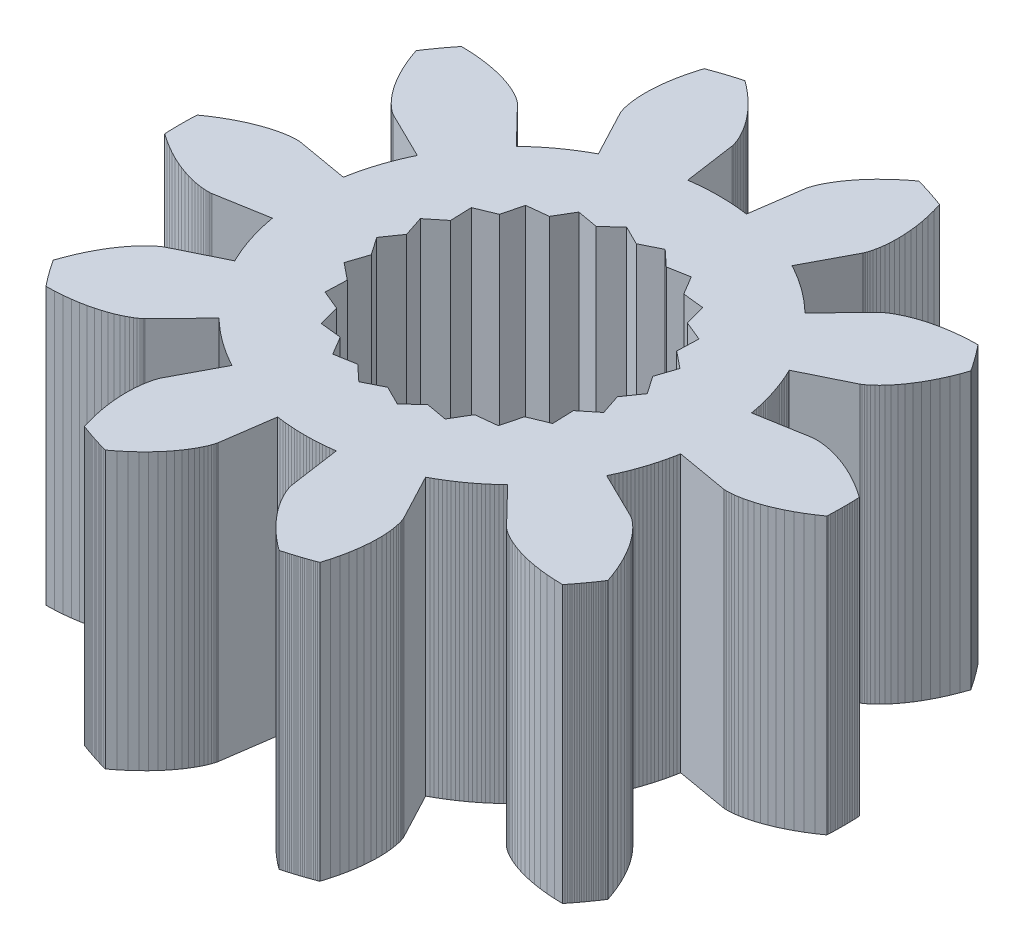
SolidWorks part; units mm, degrees
ref_plane "Front Plane" through (0, 0, 0) normal (0, 0, 1) x (1, 0, 0)
ref_plane "Top Plane" through (0, 0, 0) normal (0, 1, 0) x (1, 0, 0)
ref_plane "Right Plane" through (0, 0, 0) normal (1, 0, 0) x (0, 0, -1)
sketch "Sketch1" plane through (0, 0, 0) normal (0, 1, 0) x (1, 0, 0)
  line L0 (3.6947, -0.6418) -> (4.6291, -0.8041)
  line L1 (4.6291, -0.8041) -> (4.6332, -0.8047)
  line L2 (4.6332, -0.8047) -> (4.6455, -0.806)
  line L3 (4.6455, -0.806) -> (4.6659, -0.8073)
  line L4 (4.6659, -0.8073) -> (4.6947, -0.8081)
  line L5 (4.6947, -0.8081) -> (4.7316, -0.8074)
  line L6 (4.7316, -0.8074) -> (4.7767, -0.8048)
  line L7 (4.7767, -0.8048) -> (4.8297, -0.7994)
  line L8 (4.8297, -0.7994) -> (4.8907, -0.7907)
  line L9 (4.8907, -0.7907) -> (4.9593, -0.778)
  line L10 (4.9593, -0.778) -> (5.0353, -0.7605)
  line L11 (5.0353, -0.7605) -> (5.1184, -0.7378)
  line L12 (5.1184, -0.7378) -> (5.2084, -0.7091)
  line L13 (5.2084, -0.7091) -> (5.3047, -0.6738)
  line L14 (5.3047, -0.6738) -> (5.4071, -0.6314)
  line L15 (5.4071, -0.6314) -> (5.5151, -0.5813)
  line L16 (5.5151, -0.5813) -> (5.6282, -0.523)
  line L17 (5.6282, -0.523) -> (5.7459, -0.456)
  line L18 (5.7459, -0.456) -> (5.8676, -0.3797)
  line L19 (5.8676, -0.3797) -> (5.9928, -0.2937)
  line L20 (5.9928, -0.2937) -> (5.9942, -0.2628)
  line L21 (5.9942, -0.2628) -> (5.9955, -0.2319)
  line L22 (5.9955, -0.2319) -> (5.9966, -0.201)
  line L23 (5.9966, -0.201) -> (5.9976, -0.1701)
  line L24 (5.9976, -0.1701) -> (5.9984, -0.1392)
  line L25 (5.9984, -0.1392) -> (5.999, -0.1083)
  line L26 (5.999, -0.1083) -> (5.9995, -0.0773)
  line L27 (5.9995, -0.0773) -> (5.9998, -0.0464)
  line L28 (5.9998, -0.0464) -> (6, -0.0155)
  line L29 (6, -0.0155) -> (6, 0.0155)
  line L30 (6, 0.0155) -> (5.9998, 0.0464)
  line L31 (5.9998, 0.0464) -> (5.9995, 0.0773)
  line L32 (5.9995, 0.0773) -> (5.999, 0.1083)
  line L33 (5.999, 0.1083) -> (5.9984, 0.1392)
  line L34 (5.9984, 0.1392) -> (5.9976, 0.1701)
  line L35 (5.9976, 0.1701) -> (5.9966, 0.201)
  line L36 (5.9966, 0.201) -> (5.9955, 0.2319)
  line L37 (5.9955, 0.2319) -> (5.9942, 0.2628)
  line L38 (5.9942, 0.2628) -> (5.9928, 0.2937)
  line L39 (5.9928, 0.2937) -> (5.8676, 0.3797)
  line L40 (5.8676, 0.3797) -> (5.7459, 0.456)
  line L41 (5.7459, 0.456) -> (5.6282, 0.523)
  line L42 (5.6282, 0.523) -> (5.5151, 0.5813)
  line L43 (5.5151, 0.5813) -> (5.4071, 0.6314)
  line L44 (5.4071, 0.6314) -> (5.3047, 0.6738)
  line L45 (5.3047, 0.6738) -> (5.2084, 0.7091)
  line L46 (5.2084, 0.7091) -> (5.1184, 0.7378)
  line L47 (5.1184, 0.7378) -> (5.0353, 0.7605)
  line L48 (5.0353, 0.7605) -> (4.9593, 0.778)
  line L49 (4.9593, 0.778) -> (4.8907, 0.7907)
  line L50 (4.8907, 0.7907) -> (4.8297, 0.7994)
  line L51 (4.8297, 0.7994) -> (4.7767, 0.8048)
  line L52 (4.7767, 0.8048) -> (4.7316, 0.8074)
  line L53 (4.7316, 0.8074) -> (4.6947, 0.8081)
  line L54 (4.6947, 0.8081) -> (4.6659, 0.8073)
  line L55 (4.6659, 0.8073) -> (4.6455, 0.806)
  line L56 (4.6455, 0.806) -> (4.6332, 0.8047)
  line L57 (4.6332, 0.8047) -> (4.6291, 0.8041)
  line L58 (4.6291, 0.8041) -> (3.6947, 0.6418)
  line L59 (3.6947, 0.6418) -> (3.6847, 0.697)
  line L60 (3.6847, 0.697) -> (3.6738, 0.752)
  line L61 (3.6738, 0.752) -> (3.6621, 0.8069)
  line L62 (3.6621, 0.8069) -> (3.6497, 0.8617)
  line L63 (3.6497, 0.8617) -> (3.6364, 0.9162)
  line L64 (3.6364, 0.9162) -> (3.6222, 0.9705)
  line L65 (3.6222, 0.9705) -> (3.6073, 1.0246)
  line L66 (3.6073, 1.0246) -> (3.5916, 1.0785)
  line L67 (3.5916, 1.0785) -> (3.575, 1.1321)
  line L68 (3.575, 1.1321) -> (3.5577, 1.1855)
  line L69 (3.5577, 1.1855) -> (3.5396, 1.2386)
  line L70 (3.5396, 1.2386) -> (3.5206, 1.2914)
  line L71 (3.5206, 1.2914) -> (3.5009, 1.344)
  line L72 (3.5009, 1.344) -> (3.4804, 1.3962)
  line L73 (3.4804, 1.3962) -> (3.4591, 1.4481)
  line L74 (3.4591, 1.4481) -> (3.4371, 1.4997)
  line L75 (3.4371, 1.4997) -> (3.4142, 1.551)
  line L76 (3.4142, 1.551) -> (3.3906, 1.6019)
  line L77 (3.3906, 1.6019) -> (3.3663, 1.6525)
  line L78 (3.3663, 1.6525) -> (4.2177, 2.0704)
  line L79 (4.2177, 2.0704) -> (4.2213, 2.0723)
  line L80 (4.2213, 2.0723) -> (4.232, 2.0785)
  line L81 (4.232, 2.0785) -> (4.2494, 2.0894)
  line L82 (4.2494, 2.0894) -> (4.273, 2.1057)
  line L83 (4.273, 2.1057) -> (4.3025, 2.1279)
  line L84 (4.3025, 2.1279) -> (4.3374, 2.1566)
  line L85 (4.3374, 2.1566) -> (4.3773, 2.1921)
  line L86 (4.3773, 2.1921) -> (4.4214, 2.235)
  line L87 (4.4214, 2.235) -> (4.4694, 2.2856)
  line L88 (4.4694, 2.2856) -> (4.5207, 2.3444)
  line L89 (4.5207, 2.3444) -> (4.5746, 2.4117)
  line L90 (4.5746, 2.4117) -> (4.6304, 2.4877)
  line L91 (4.6304, 2.4877) -> (4.6877, 2.5729)
  line L92 (4.6877, 2.5729) -> (4.7456, 2.6674)
  line L93 (4.7456, 2.6674) -> (4.8035, 2.7714)
  line L94 (4.8035, 2.7714) -> (4.8607, 2.885)
  line L95 (4.8607, 2.885) -> (4.9165, 3.0085)
  line L96 (4.9165, 3.0085) -> (4.9702, 3.1417)
  line L97 (4.9702, 3.1417) -> (5.0209, 3.2848)
  line L98 (5.0209, 3.2848) -> (5.0039, 3.3107)
  line L99 (5.0039, 3.3107) -> (4.9868, 3.3364)
  line L100 (4.9868, 3.3364) -> (4.9695, 3.3621)
  line L101 (4.9695, 3.3621) -> (4.9521, 3.3877)
  line L102 (4.9521, 3.3877) -> (4.9346, 3.4132)
  line L103 (4.9346, 3.4132) -> (4.9169, 3.4386)
  line L104 (4.9169, 3.4386) -> (4.8992, 3.4639)
  line L105 (4.8992, 3.4639) -> (4.8812, 3.4891)
  line L106 (4.8812, 3.4891) -> (4.8632, 3.5142)
  line L107 (4.8632, 3.5142) -> (4.845, 3.5392)
  line L108 (4.845, 3.5392) -> (4.8267, 3.5641)
  line L109 (4.8267, 3.5641) -> (4.8082, 3.589)
  line L110 (4.8082, 3.589) -> (4.7897, 3.6137)
  line L111 (4.7897, 3.6137) -> (4.771, 3.6384)
  line L112 (4.771, 3.6384) -> (4.7522, 3.6629)
  line L113 (4.7522, 3.6629) -> (4.7332, 3.6874)
  line L114 (4.7332, 3.6874) -> (4.7141, 3.7117)
  line L115 (4.7141, 3.7117) -> (4.6949, 3.736)
  line L116 (4.6949, 3.736) -> (4.6756, 3.7601)
  line L117 (4.6756, 3.7601) -> (4.5238, 3.7561)
  line L118 (4.5238, 3.7561) -> (4.3805, 3.7462)
  line L119 (4.3805, 3.7462) -> (4.2459, 3.7313)
  line L120 (4.2459, 3.7313) -> (4.1201, 3.712)
  line L121 (4.1201, 3.712) -> (4.0033, 3.6891)
  line L122 (4.0033, 3.6891) -> (3.8956, 3.6632)
  line L123 (3.8956, 3.6632) -> (3.7969, 3.6351)
  line L124 (3.7969, 3.6351) -> (3.7072, 3.6054)
  line L125 (3.7072, 3.6054) -> (3.6266, 3.575)
  line L126 (3.6266, 3.575) -> (3.5549, 3.5444)
  line L127 (3.5549, 3.5444) -> (3.4919, 3.5144)
  line L128 (3.4919, 3.5144) -> (3.4374, 3.4856)
  line L129 (3.4374, 3.4856) -> (3.3914, 3.4587)
  line L130 (3.3914, 3.4587) -> (3.3533, 3.4344)
  line L131 (3.3533, 3.4344) -> (3.3231, 3.4132)
  line L132 (3.3231, 3.4132) -> (3.3003, 3.3957)
  line L133 (3.3003, 3.3957) -> (3.2845, 3.3826)
  line L134 (3.2845, 3.3826) -> (3.2754, 3.3743)
  line L135 (3.2754, 3.3743) -> (3.2724, 3.3715)
  line L136 (3.2724, 3.3715) -> (2.6118, 2.6909)
  line L137 (2.6118, 2.6909) -> (2.5713, 2.7297)
  line L138 (2.5713, 2.7297) -> (2.5301, 2.7678)
  line L139 (2.5301, 2.7678) -> (2.4884, 2.8054)
  line L140 (2.4884, 2.8054) -> (2.4462, 2.8423)
  line L141 (2.4462, 2.8423) -> (2.4034, 2.8786)
  line L142 (2.4034, 2.8786) -> (2.36, 2.9142)
  line L143 (2.36, 2.9142) -> (2.3161, 2.9492)
  line L144 (2.3161, 2.9492) -> (2.2717, 2.9836)
  line L145 (2.2717, 2.9836) -> (2.2268, 3.0172)
  line L146 (2.2268, 3.0172) -> (2.1814, 3.0502)
  line L147 (2.1814, 3.0502) -> (2.1355, 3.0825)
  line L148 (2.1355, 3.0825) -> (2.0892, 3.1141)
  line L149 (2.0892, 3.1141) -> (2.0423, 3.1451)
  line L150 (2.0423, 3.1451) -> (1.995, 3.1753)
  line L151 (1.995, 3.1753) -> (1.9473, 3.2048)
  line L152 (1.9473, 3.2048) -> (1.8991, 3.2336)
  line L153 (1.8991, 3.2336) -> (1.8505, 3.2616)
  line L154 (1.8505, 3.2616) -> (1.8015, 3.2889)
  line L155 (1.8015, 3.2889) -> (1.7521, 3.3155)
  line L156 (1.7521, 3.3155) -> (2.1952, 4.1541)
  line L157 (2.1952, 4.1541) -> (2.197, 4.1578)
  line L158 (2.197, 4.1578) -> (2.2021, 4.169)
  line L159 (2.2021, 4.169) -> (2.2097, 4.1881)
  line L160 (2.2097, 4.1881) -> (2.2192, 4.2152)
  line L161 (2.2192, 4.2152) -> (2.23, 4.2505)
  line L162 (2.23, 4.2505) -> (2.2415, 4.2942)
  line L163 (2.2415, 4.2942) -> (2.2528, 4.3463)
  line L164 (2.2528, 4.3463) -> (2.2633, 4.407)
  line L165 (2.2633, 4.407) -> (2.2724, 4.4762)
  line L166 (2.2724, 4.4762) -> (2.2793, 4.5538)
  line L167 (2.2793, 4.5538) -> (2.2834, 4.6399)
  line L168 (2.2834, 4.6399) -> (2.2838, 4.7343)
  line L169 (2.2838, 4.7343) -> (2.2801, 4.8369)
  line L170 (2.2801, 4.8369) -> (2.2714, 4.9474)
  line L171 (2.2714, 4.9474) -> (2.2571, 5.0655)
  line L172 (2.2571, 5.0655) -> (2.2366, 5.1911)
  line L173 (2.2366, 5.1911) -> (2.2092, 5.3237)
  line L174 (2.2092, 5.3237) -> (2.1743, 5.4631)
  line L175 (2.1743, 5.4631) -> (2.1312, 5.6087)
  line L176 (2.1312, 5.6087) -> (2.1023, 5.6196)
  line L177 (2.1023, 5.6196) -> (2.0733, 5.6304)
  line L178 (2.0733, 5.6304) -> (2.0442, 5.641)
  line L179 (2.0442, 5.641) -> (2.0151, 5.6515)
  line L180 (2.0151, 5.6515) -> (1.986, 5.6618)
  line L181 (1.986, 5.6618) -> (1.9568, 5.672)
  line L182 (1.9568, 5.672) -> (1.9275, 5.682)
  line L183 (1.9275, 5.682) -> (1.8982, 5.6918)
  line L184 (1.8982, 5.6918) -> (1.8688, 5.7015)
  line L185 (1.8688, 5.7015) -> (1.8394, 5.7111)
  line L186 (1.8394, 5.7111) -> (1.8099, 5.7205)
  line L187 (1.8099, 5.7205) -> (1.7804, 5.7298)
  line L188 (1.7804, 5.7298) -> (1.7508, 5.7389)
  line L189 (1.7508, 5.7389) -> (1.7212, 5.7478)
  line L190 (1.7212, 5.7478) -> (1.6916, 5.7566)
  line L191 (1.6916, 5.7566) -> (1.6619, 5.7653)
  line L192 (1.6619, 5.7653) -> (1.6321, 5.7737)
  line L193 (1.6321, 5.7737) -> (1.6023, 5.7821)
  line L194 (1.6023, 5.7821) -> (1.5725, 5.7903)
  line L195 (1.5725, 5.7903) -> (1.4521, 5.6977)
  line L196 (1.4521, 5.6977) -> (1.3419, 5.6055)
  line L197 (1.3419, 5.6055) -> (1.2418, 5.5143)
  line L198 (1.2418, 5.5143) -> (1.1514, 5.4248)
  line L199 (1.1514, 5.4248) -> (1.0704, 5.3376)
  line L200 (1.0704, 5.3376) -> (0.9984, 5.2533)
  line L201 (0.9984, 5.2533) -> (0.9351, 5.1726)
  line L202 (0.9351, 5.1726) -> (0.88, 5.0959)
  line L203 (0.88, 5.0959) -> (0.8327, 5.0239)
  line L204 (0.8327, 5.0239) -> (0.7926, 4.957)
  line L205 (0.7926, 4.957) -> (0.7593, 4.8957)
  line L206 (0.7593, 4.8957) -> (0.7322, 4.8404)
  line L207 (0.7322, 4.8404) -> (0.7107, 4.7916)
  line L208 (0.7107, 4.7916) -> (0.6942, 4.7495)
  line L209 (0.6942, 4.7495) -> (0.6822, 4.7146)
  line L210 (0.6822, 4.7146) -> (0.674, 4.687)
  line L211 (0.674, 4.687) -> (0.669, 4.6672)
  line L212 (0.669, 4.6672) -> (0.6665, 4.6551)
  line L213 (0.6665, 4.6551) -> (0.6658, 4.6511)
  line L214 (0.6658, 4.6511) -> (0.5314, 3.7122)
  line L215 (0.5314, 3.7122) -> (0.4757, 3.7197)
  line L216 (0.4757, 3.7197) -> (0.42, 3.7264)
  line L217 (0.42, 3.7264) -> (0.3642, 3.7323)
  line L218 (0.3642, 3.7323) -> (0.3083, 3.7373)
  line L219 (0.3083, 3.7373) -> (0.2524, 3.7415)
  line L220 (0.2524, 3.7415) -> (0.1963, 3.7449)
  line L221 (0.1963, 3.7449) -> (0.1403, 3.7474)
  line L222 (0.1403, 3.7474) -> (0.0842, 3.7491)
  line L223 (0.0842, 3.7491) -> (0.0281, 3.7499)
  line L224 (0.0281, 3.7499) -> (-0.0281, 3.7499)
  line L225 (-0.0281, 3.7499) -> (-0.0842, 3.7491)
  line L226 (-0.0842, 3.7491) -> (-0.1403, 3.7474)
  line L227 (-0.1403, 3.7474) -> (-0.1963, 3.7449)
  line L228 (-0.1963, 3.7449) -> (-0.2524, 3.7415)
  line L229 (-0.2524, 3.7415) -> (-0.3083, 3.7373)
  line L230 (-0.3083, 3.7373) -> (-0.3642, 3.7323)
  line L231 (-0.3642, 3.7323) -> (-0.42, 3.7264)
  line L232 (-0.42, 3.7264) -> (-0.4757, 3.7197)
  line L233 (-0.4757, 3.7197) -> (-0.5314, 3.7122)
  line L234 (-0.5314, 3.7122) -> (-0.6658, 4.6511)
  line L235 (-0.6658, 4.6511) -> (-0.6665, 4.6551)
  line L236 (-0.6665, 4.6551) -> (-0.669, 4.6672)
  line L237 (-0.669, 4.6672) -> (-0.674, 4.687)
  line L238 (-0.674, 4.687) -> (-0.6822, 4.7146)
  line L239 (-0.6822, 4.7146) -> (-0.6942, 4.7495)
  line L240 (-0.6942, 4.7495) -> (-0.7107, 4.7916)
  line L241 (-0.7107, 4.7916) -> (-0.7322, 4.8404)
  line L242 (-0.7322, 4.8404) -> (-0.7593, 4.8957)
  line L243 (-0.7593, 4.8957) -> (-0.7926, 4.957)
  line L244 (-0.7926, 4.957) -> (-0.8327, 5.0239)
  line L245 (-0.8327, 5.0239) -> (-0.88, 5.0959)
  line L246 (-0.88, 5.0959) -> (-0.9351, 5.1726)
  line L247 (-0.9351, 5.1726) -> (-0.9984, 5.2533)
  line L248 (-0.9984, 5.2533) -> (-1.0704, 5.3376)
  line L249 (-1.0704, 5.3376) -> (-1.1514, 5.4248)
  line L250 (-1.1514, 5.4248) -> (-1.2418, 5.5143)
  line L251 (-1.2418, 5.5143) -> (-1.3419, 5.6055)
  line L252 (-1.3419, 5.6055) -> (-1.4521, 5.6977)
  line L253 (-1.4521, 5.6977) -> (-1.5725, 5.7903)
  line L254 (-1.5725, 5.7903) -> (-1.6023, 5.7821)
  line L255 (-1.6023, 5.7821) -> (-1.6321, 5.7737)
  line L256 (-1.6321, 5.7737) -> (-1.6619, 5.7653)
  line L257 (-1.6619, 5.7653) -> (-1.6916, 5.7566)
  line L258 (-1.6916, 5.7566) -> (-1.7212, 5.7478)
  line L259 (-1.7212, 5.7478) -> (-1.7508, 5.7389)
  line L260 (-1.7508, 5.7389) -> (-1.7804, 5.7298)
  line L261 (-1.7804, 5.7298) -> (-1.8099, 5.7205)
  line L262 (-1.8099, 5.7205) -> (-1.8394, 5.7111)
  line L263 (-1.8394, 5.7111) -> (-1.8688, 5.7015)
  line L264 (-1.8688, 5.7015) -> (-1.8982, 5.6918)
  line L265 (-1.8982, 5.6918) -> (-1.9275, 5.682)
  line L266 (-1.9275, 5.682) -> (-1.9568, 5.672)
  line L267 (-1.9568, 5.672) -> (-1.986, 5.6618)
  line L268 (-1.986, 5.6618) -> (-2.0151, 5.6515)
  line L269 (-2.0151, 5.6515) -> (-2.0442, 5.641)
  line L270 (-2.0442, 5.641) -> (-2.0733, 5.6304)
  line L271 (-2.0733, 5.6304) -> (-2.1023, 5.6196)
  line L272 (-2.1023, 5.6196) -> (-2.1312, 5.6087)
  line L273 (-2.1312, 5.6087) -> (-2.1743, 5.4631)
  line L274 (-2.1743, 5.4631) -> (-2.2092, 5.3237)
  line L275 (-2.2092, 5.3237) -> (-2.2366, 5.1911)
  line L276 (-2.2366, 5.1911) -> (-2.2571, 5.0655)
  line L277 (-2.2571, 5.0655) -> (-2.2714, 4.9474)
  line L278 (-2.2714, 4.9474) -> (-2.2801, 4.8369)
  line L279 (-2.2801, 4.8369) -> (-2.2838, 4.7343)
  line L280 (-2.2838, 4.7343) -> (-2.2834, 4.6399)
  line L281 (-2.2834, 4.6399) -> (-2.2793, 4.5538)
  line L282 (-2.2793, 4.5538) -> (-2.2724, 4.4762)
  line L283 (-2.2724, 4.4762) -> (-2.2633, 4.407)
  line L284 (-2.2633, 4.407) -> (-2.2528, 4.3463)
  line L285 (-2.2528, 4.3463) -> (-2.2415, 4.2942)
  line L286 (-2.2415, 4.2942) -> (-2.23, 4.2505)
  line L287 (-2.23, 4.2505) -> (-2.2192, 4.2152)
  line L288 (-2.2192, 4.2152) -> (-2.2097, 4.1881)
  line L289 (-2.2097, 4.1881) -> (-2.2021, 4.169)
  line L290 (-2.2021, 4.169) -> (-2.197, 4.1578)
  line L291 (-2.197, 4.1578) -> (-2.1952, 4.1541)
  line L292 (-2.1952, 4.1541) -> (-1.7521, 3.3155)
  line L293 (-1.7521, 3.3155) -> (-1.8015, 3.2889)
  line L294 (-1.8015, 3.2889) -> (-1.8505, 3.2616)
  line L295 (-1.8505, 3.2616) -> (-1.8991, 3.2336)
  line L296 (-1.8991, 3.2336) -> (-1.9473, 3.2048)
  line L297 (-1.9473, 3.2048) -> (-1.995, 3.1753)
  line L298 (-1.995, 3.1753) -> (-2.0423, 3.1451)
  line L299 (-2.0423, 3.1451) -> (-2.0892, 3.1141)
  line L300 (-2.0892, 3.1141) -> (-2.1355, 3.0825)
  line L301 (-2.1355, 3.0825) -> (-2.1814, 3.0502)
  line L302 (-2.1814, 3.0502) -> (-2.2268, 3.0172)
  line L303 (-2.2268, 3.0172) -> (-2.2717, 2.9836)
  line L304 (-2.2717, 2.9836) -> (-2.3161, 2.9492)
  line L305 (-2.3161, 2.9492) -> (-2.36, 2.9142)
  line L306 (-2.36, 2.9142) -> (-2.4034, 2.8786)
  line L307 (-2.4034, 2.8786) -> (-2.4462, 2.8423)
  line L308 (-2.4462, 2.8423) -> (-2.4884, 2.8054)
  line L309 (-2.4884, 2.8054) -> (-2.5301, 2.7678)
  line L310 (-2.5301, 2.7678) -> (-2.5713, 2.7297)
  line L311 (-2.5713, 2.7297) -> (-2.6118, 2.6909)
  line L312 (-2.6118, 2.6909) -> (-3.2724, 3.3715)
  line L313 (-3.2724, 3.3715) -> (-3.2754, 3.3743)
  line L314 (-3.2754, 3.3743) -> (-3.2845, 3.3826)
  line L315 (-3.2845, 3.3826) -> (-3.3003, 3.3957)
  line L316 (-3.3003, 3.3957) -> (-3.3231, 3.4132)
  line L317 (-3.3231, 3.4132) -> (-3.3533, 3.4344)
  line L318 (-3.3533, 3.4344) -> (-3.3914, 3.4587)
  line L319 (-3.3914, 3.4587) -> (-3.4374, 3.4856)
  line L320 (-3.4374, 3.4856) -> (-3.4919, 3.5144)
  line L321 (-3.4919, 3.5144) -> (-3.5549, 3.5444)
  line L322 (-3.5549, 3.5444) -> (-3.6266, 3.575)
  line L323 (-3.6266, 3.575) -> (-3.7072, 3.6054)
  line L324 (-3.7072, 3.6054) -> (-3.7969, 3.6351)
  line L325 (-3.7969, 3.6351) -> (-3.8956, 3.6632)
  line L326 (-3.8956, 3.6632) -> (-4.0033, 3.6891)
  line L327 (-4.0033, 3.6891) -> (-4.1201, 3.712)
  line L328 (-4.1201, 3.712) -> (-4.2459, 3.7313)
  line L329 (-4.2459, 3.7313) -> (-4.3805, 3.7462)
  line L330 (-4.3805, 3.7462) -> (-4.5238, 3.7561)
  line L331 (-4.5238, 3.7561) -> (-4.6756, 3.7601)
  line L332 (-4.6756, 3.7601) -> (-4.6949, 3.736)
  line L333 (-4.6949, 3.736) -> (-4.7141, 3.7117)
  line L334 (-4.7141, 3.7117) -> (-4.7332, 3.6874)
  line L335 (-4.7332, 3.6874) -> (-4.7522, 3.6629)
  line L336 (-4.7522, 3.6629) -> (-4.771, 3.6384)
  line L337 (-4.771, 3.6384) -> (-4.7897, 3.6137)
  line L338 (-4.7897, 3.6137) -> (-4.8082, 3.589)
  line L339 (-4.8082, 3.589) -> (-4.8267, 3.5641)
  line L340 (-4.8267, 3.5641) -> (-4.845, 3.5392)
  line L341 (-4.845, 3.5392) -> (-4.8632, 3.5142)
  line L342 (-4.8632, 3.5142) -> (-4.8812, 3.4891)
  line L343 (-4.8812, 3.4891) -> (-4.8992, 3.4639)
  line L344 (-4.8992, 3.4639) -> (-4.9169, 3.4386)
  line L345 (-4.9169, 3.4386) -> (-4.9346, 3.4132)
  line L346 (-4.9346, 3.4132) -> (-4.9521, 3.3877)
  line L347 (-4.9521, 3.3877) -> (-4.9695, 3.3621)
  line L348 (-4.9695, 3.3621) -> (-4.9868, 3.3364)
  line L349 (-4.9868, 3.3364) -> (-5.0039, 3.3107)
  line L350 (-5.0039, 3.3107) -> (-5.0209, 3.2848)
  line L351 (-5.0209, 3.2848) -> (-4.9702, 3.1417)
  line L352 (-4.9702, 3.1417) -> (-4.9165, 3.0085)
  line L353 (-4.9165, 3.0085) -> (-4.8607, 2.885)
  line L354 (-4.8607, 2.885) -> (-4.8035, 2.7714)
  line L355 (-4.8035, 2.7714) -> (-4.7456, 2.6674)
  line L356 (-4.7456, 2.6674) -> (-4.6877, 2.5729)
  line L357 (-4.6877, 2.5729) -> (-4.6304, 2.4877)
  line L358 (-4.6304, 2.4877) -> (-4.5746, 2.4117)
  line L359 (-4.5746, 2.4117) -> (-4.5207, 2.3444)
  line L360 (-4.5207, 2.3444) -> (-4.4694, 2.2856)
  line L361 (-4.4694, 2.2856) -> (-4.4214, 2.235)
  line L362 (-4.4214, 2.235) -> (-4.3773, 2.1921)
  line L363 (-4.3773, 2.1921) -> (-4.3374, 2.1566)
  line L364 (-4.3374, 2.1566) -> (-4.3025, 2.1279)
  line L365 (-4.3025, 2.1279) -> (-4.273, 2.1057)
  line L366 (-4.273, 2.1057) -> (-4.2494, 2.0894)
  line L367 (-4.2494, 2.0894) -> (-4.232, 2.0785)
  line L368 (-4.232, 2.0785) -> (-4.2213, 2.0723)
  line L369 (-4.2213, 2.0723) -> (-4.2177, 2.0704)
  line L370 (-4.2177, 2.0704) -> (-3.3663, 1.6525)
  line L371 (-3.3663, 1.6525) -> (-3.3906, 1.6019)
  line L372 (-3.3906, 1.6019) -> (-3.4142, 1.551)
  line L373 (-3.4142, 1.551) -> (-3.4371, 1.4997)
  line L374 (-3.4371, 1.4997) -> (-3.4591, 1.4481)
  line L375 (-3.4591, 1.4481) -> (-3.4804, 1.3962)
  line L376 (-3.4804, 1.3962) -> (-3.5009, 1.344)
  line L377 (-3.5009, 1.344) -> (-3.5206, 1.2914)
  line L378 (-3.5206, 1.2914) -> (-3.5396, 1.2386)
  line L379 (-3.5396, 1.2386) -> (-3.5577, 1.1855)
  line L380 (-3.5577, 1.1855) -> (-3.575, 1.1321)
  line L381 (-3.575, 1.1321) -> (-3.5916, 1.0785)
  line L382 (-3.5916, 1.0785) -> (-3.6073, 1.0246)
  line L383 (-3.6073, 1.0246) -> (-3.6222, 0.9705)
  line L384 (-3.6222, 0.9705) -> (-3.6364, 0.9162)
  line L385 (-3.6364, 0.9162) -> (-3.6497, 0.8617)
  line L386 (-3.6497, 0.8617) -> (-3.6621, 0.8069)
  line L387 (-3.6621, 0.8069) -> (-3.6738, 0.752)
  line L388 (-3.6738, 0.752) -> (-3.6847, 0.697)
  line L389 (-3.6847, 0.697) -> (-3.6947, 0.6418)
  line L390 (-3.6947, 0.6418) -> (-4.6291, 0.8041)
  line L391 (-4.6291, 0.8041) -> (-4.6332, 0.8047)
  line L392 (-4.6332, 0.8047) -> (-4.6455, 0.806)
  line L393 (-4.6455, 0.806) -> (-4.6659, 0.8073)
  line L394 (-4.6659, 0.8073) -> (-4.6947, 0.8081)
  line L395 (-4.6947, 0.8081) -> (-4.7316, 0.8074)
  line L396 (-4.7316, 0.8074) -> (-4.7767, 0.8048)
  line L397 (-4.7767, 0.8048) -> (-4.8297, 0.7994)
  line L398 (-4.8297, 0.7994) -> (-4.8907, 0.7907)
  line L399 (-4.8907, 0.7907) -> (-4.9593, 0.778)
  line L400 (-4.9593, 0.778) -> (-5.0353, 0.7605)
  line L401 (-5.0353, 0.7605) -> (-5.1184, 0.7378)
  line L402 (-5.1184, 0.7378) -> (-5.2084, 0.7091)
  line L403 (-5.2084, 0.7091) -> (-5.3047, 0.6738)
  line L404 (-5.3047, 0.6738) -> (-5.4071, 0.6314)
  line L405 (-5.4071, 0.6314) -> (-5.5151, 0.5813)
  line L406 (-5.5151, 0.5813) -> (-5.6282, 0.523)
  line L407 (-5.6282, 0.523) -> (-5.7459, 0.456)
  line L408 (-5.7459, 0.456) -> (-5.8676, 0.3797)
  line L409 (-5.8676, 0.3797) -> (-5.9928, 0.2937)
  line L410 (-5.9928, 0.2937) -> (-5.9942, 0.2628)
  line L411 (-5.9942, 0.2628) -> (-5.9955, 0.2319)
  line L412 (-5.9955, 0.2319) -> (-5.9966, 0.201)
  line L413 (-5.9966, 0.201) -> (-5.9976, 0.1701)
  line L414 (-5.9976, 0.1701) -> (-5.9984, 0.1392)
  line L415 (-5.9984, 0.1392) -> (-5.999, 0.1083)
  line L416 (-5.999, 0.1083) -> (-5.9995, 0.0773)
  line L417 (-5.9995, 0.0773) -> (-5.9998, 0.0464)
  line L418 (-5.9998, 0.0464) -> (-6, 0.0155)
  line L419 (-6, 0.0155) -> (-6, -0.0155)
  line L420 (-6, -0.0155) -> (-5.9998, -0.0464)
  line L421 (-5.9998, -0.0464) -> (-5.9995, -0.0773)
  line L422 (-5.9995, -0.0773) -> (-5.999, -0.1083)
  line L423 (-5.999, -0.1083) -> (-5.9984, -0.1392)
  line L424 (-5.9984, -0.1392) -> (-5.9976, -0.1701)
  line L425 (-5.9976, -0.1701) -> (-5.9966, -0.201)
  line L426 (-5.9966, -0.201) -> (-5.9955, -0.2319)
  line L427 (-5.9955, -0.2319) -> (-5.9942, -0.2628)
  line L428 (-5.9942, -0.2628) -> (-5.9928, -0.2937)
  line L429 (-5.9928, -0.2937) -> (-5.8676, -0.3797)
  line L430 (-5.8676, -0.3797) -> (-5.7459, -0.456)
  line L431 (-5.7459, -0.456) -> (-5.6282, -0.523)
  line L432 (-5.6282, -0.523) -> (-5.5151, -0.5813)
  line L433 (-5.5151, -0.5813) -> (-5.4071, -0.6314)
  line L434 (-5.4071, -0.6314) -> (-5.3047, -0.6738)
  line L435 (-5.3047, -0.6738) -> (-5.2084, -0.7091)
  line L436 (-5.2084, -0.7091) -> (-5.1184, -0.7378)
  line L437 (-5.1184, -0.7378) -> (-5.0353, -0.7605)
  line L438 (-5.0353, -0.7605) -> (-4.9593, -0.778)
  line L439 (-4.9593, -0.778) -> (-4.8907, -0.7907)
  line L440 (-4.8907, -0.7907) -> (-4.8297, -0.7994)
  line L441 (-4.8297, -0.7994) -> (-4.7767, -0.8048)
  line L442 (-4.7767, -0.8048) -> (-4.7316, -0.8074)
  line L443 (-4.7316, -0.8074) -> (-4.6947, -0.8081)
  line L444 (-4.6947, -0.8081) -> (-4.6659, -0.8073)
  line L445 (-4.6659, -0.8073) -> (-4.6455, -0.806)
  line L446 (-4.6455, -0.806) -> (-4.6332, -0.8047)
  line L447 (-4.6332, -0.8047) -> (-4.6291, -0.8041)
  line L448 (-4.6291, -0.8041) -> (-3.6947, -0.6418)
  line L449 (-3.6947, -0.6418) -> (-3.6847, -0.697)
  line L450 (-3.6847, -0.697) -> (-3.6738, -0.752)
  line L451 (-3.6738, -0.752) -> (-3.6621, -0.8069)
  line L452 (-3.6621, -0.8069) -> (-3.6497, -0.8617)
  line L453 (-3.6497, -0.8617) -> (-3.6364, -0.9162)
  line L454 (-3.6364, -0.9162) -> (-3.6222, -0.9705)
  line L455 (-3.6222, -0.9705) -> (-3.6073, -1.0246)
  line L456 (-3.6073, -1.0246) -> (-3.5916, -1.0785)
  line L457 (-3.5916, -1.0785) -> (-3.575, -1.1321)
  line L458 (-3.575, -1.1321) -> (-3.5577, -1.1855)
  line L459 (-3.5577, -1.1855) -> (-3.5396, -1.2386)
  line L460 (-3.5396, -1.2386) -> (-3.5206, -1.2914)
  line L461 (-3.5206, -1.2914) -> (-3.5009, -1.344)
  line L462 (-3.5009, -1.344) -> (-3.4804, -1.3962)
  line L463 (-3.4804, -1.3962) -> (-3.4591, -1.4481)
  line L464 (-3.4591, -1.4481) -> (-3.4371, -1.4997)
  line L465 (-3.4371, -1.4997) -> (-3.4142, -1.551)
  line L466 (-3.4142, -1.551) -> (-3.3906, -1.6019)
  line L467 (-3.3906, -1.6019) -> (-3.3663, -1.6525)
  line L468 (-3.3663, -1.6525) -> (-4.2177, -2.0704)
  line L469 (-4.2177, -2.0704) -> (-4.2213, -2.0723)
  line L470 (-4.2213, -2.0723) -> (-4.232, -2.0785)
  line L471 (-4.232, -2.0785) -> (-4.2494, -2.0894)
  line L472 (-4.2494, -2.0894) -> (-4.273, -2.1057)
  line L473 (-4.273, -2.1057) -> (-4.3025, -2.1279)
  line L474 (-4.3025, -2.1279) -> (-4.3374, -2.1566)
  line L475 (-4.3374, -2.1566) -> (-4.3773, -2.1921)
  line L476 (-4.3773, -2.1921) -> (-4.4214, -2.235)
  line L477 (-4.4214, -2.235) -> (-4.4694, -2.2856)
  line L478 (-4.4694, -2.2856) -> (-4.5207, -2.3444)
  line L479 (-4.5207, -2.3444) -> (-4.5746, -2.4117)
  line L480 (-4.5746, -2.4117) -> (-4.6304, -2.4877)
  line L481 (-4.6304, -2.4877) -> (-4.6877, -2.5729)
  line L482 (-4.6877, -2.5729) -> (-4.7456, -2.6674)
  line L483 (-4.7456, -2.6674) -> (-4.8035, -2.7714)
  line L484 (-4.8035, -2.7714) -> (-4.8607, -2.885)
  line L485 (-4.8607, -2.885) -> (-4.9165, -3.0085)
  line L486 (-4.9165, -3.0085) -> (-4.9702, -3.1417)
  line L487 (-4.9702, -3.1417) -> (-5.0209, -3.2848)
  line L488 (-5.0209, -3.2848) -> (-5.0039, -3.3107)
  line L489 (-5.0039, -3.3107) -> (-4.9868, -3.3364)
  line L490 (-4.9868, -3.3364) -> (-4.9695, -3.3621)
  line L491 (-4.9695, -3.3621) -> (-4.9521, -3.3877)
  line L492 (-4.9521, -3.3877) -> (-4.9346, -3.4132)
  line L493 (-4.9346, -3.4132) -> (-4.9169, -3.4386)
  line L494 (-4.9169, -3.4386) -> (-4.8992, -3.4639)
  line L495 (-4.8992, -3.4639) -> (-4.8812, -3.4891)
  line L496 (-4.8812, -3.4891) -> (-4.8632, -3.5142)
  line L497 (-4.8632, -3.5142) -> (-4.845, -3.5392)
  line L498 (-4.845, -3.5392) -> (-4.8267, -3.5641)
  line L499 (-4.8267, -3.5641) -> (-4.8082, -3.589)
  line L500 (-4.8082, -3.589) -> (-4.7897, -3.6137)
  line L501 (-4.7897, -3.6137) -> (-4.771, -3.6384)
  line L502 (-4.771, -3.6384) -> (-4.7522, -3.6629)
  line L503 (-4.7522, -3.6629) -> (-4.7332, -3.6874)
  line L504 (-4.7332, -3.6874) -> (-4.7141, -3.7117)
  line L505 (-4.7141, -3.7117) -> (-4.6949, -3.736)
  line L506 (-4.6949, -3.736) -> (-4.6756, -3.7601)
  line L507 (-4.6756, -3.7601) -> (-4.5238, -3.7561)
  line L508 (-4.5238, -3.7561) -> (-4.3805, -3.7462)
  line L509 (-4.3805, -3.7462) -> (-4.2459, -3.7313)
  line L510 (-4.2459, -3.7313) -> (-4.1201, -3.712)
  line L511 (-4.1201, -3.712) -> (-4.0033, -3.6891)
  line L512 (-4.0033, -3.6891) -> (-3.8956, -3.6632)
  line L513 (-3.8956, -3.6632) -> (-3.7969, -3.6351)
  line L514 (-3.7969, -3.6351) -> (-3.7072, -3.6054)
  line L515 (-3.7072, -3.6054) -> (-3.6266, -3.575)
  line L516 (-3.6266, -3.575) -> (-3.5549, -3.5444)
  line L517 (-3.5549, -3.5444) -> (-3.4919, -3.5144)
  line L518 (-3.4919, -3.5144) -> (-3.4374, -3.4856)
  line L519 (-3.4374, -3.4856) -> (-3.3914, -3.4587)
  line L520 (-3.3914, -3.4587) -> (-3.3533, -3.4344)
  line L521 (-3.3533, -3.4344) -> (-3.3231, -3.4132)
  line L522 (-3.3231, -3.4132) -> (-3.3003, -3.3957)
  line L523 (-3.3003, -3.3957) -> (-3.2845, -3.3826)
  line L524 (-3.2845, -3.3826) -> (-3.2754, -3.3743)
  line L525 (-3.2754, -3.3743) -> (-3.2724, -3.3715)
  line L526 (-3.2724, -3.3715) -> (-2.6118, -2.6909)
  line L527 (-2.6118, -2.6909) -> (-2.5713, -2.7297)
  line L528 (-2.5713, -2.7297) -> (-2.5301, -2.7678)
  line L529 (-2.5301, -2.7678) -> (-2.4884, -2.8054)
  line L530 (-2.4884, -2.8054) -> (-2.4462, -2.8423)
  line L531 (-2.4462, -2.8423) -> (-2.4034, -2.8786)
  line L532 (-2.4034, -2.8786) -> (-2.36, -2.9142)
  line L533 (-2.36, -2.9142) -> (-2.3161, -2.9492)
  line L534 (-2.3161, -2.9492) -> (-2.2717, -2.9836)
  line L535 (-2.2717, -2.9836) -> (-2.2268, -3.0172)
  line L536 (-2.2268, -3.0172) -> (-2.1814, -3.0502)
  line L537 (-2.1814, -3.0502) -> (-2.1355, -3.0825)
  line L538 (-2.1355, -3.0825) -> (-2.0892, -3.1141)
  line L539 (-2.0892, -3.1141) -> (-2.0423, -3.1451)
  line L540 (-2.0423, -3.1451) -> (-1.995, -3.1753)
  line L541 (-1.995, -3.1753) -> (-1.9473, -3.2048)
  line L542 (-1.9473, -3.2048) -> (-1.8991, -3.2336)
  line L543 (-1.8991, -3.2336) -> (-1.8505, -3.2616)
  line L544 (-1.8505, -3.2616) -> (-1.8015, -3.2889)
  line L545 (-1.8015, -3.2889) -> (-1.7521, -3.3155)
  line L546 (-1.7521, -3.3155) -> (-2.1952, -4.1541)
  line L547 (-2.1952, -4.1541) -> (-2.197, -4.1578)
  line L548 (-2.197, -4.1578) -> (-2.2021, -4.169)
  line L549 (-2.2021, -4.169) -> (-2.2097, -4.1881)
  line L550 (-2.2097, -4.1881) -> (-2.2192, -4.2152)
  line L551 (-2.2192, -4.2152) -> (-2.23, -4.2505)
  line L552 (-2.23, -4.2505) -> (-2.2415, -4.2942)
  line L553 (-2.2415, -4.2942) -> (-2.2528, -4.3463)
  line L554 (-2.2528, -4.3463) -> (-2.2633, -4.407)
  line L555 (-2.2633, -4.407) -> (-2.2724, -4.4762)
  line L556 (-2.2724, -4.4762) -> (-2.2793, -4.5538)
  line L557 (-2.2793, -4.5538) -> (-2.2834, -4.6399)
  line L558 (-2.2834, -4.6399) -> (-2.2838, -4.7343)
  line L559 (-2.2838, -4.7343) -> (-2.2801, -4.8369)
  line L560 (-2.2801, -4.8369) -> (-2.2714, -4.9474)
  line L561 (-2.2714, -4.9474) -> (-2.2571, -5.0655)
  line L562 (-2.2571, -5.0655) -> (-2.2366, -5.1911)
  line L563 (-2.2366, -5.1911) -> (-2.2092, -5.3237)
  line L564 (-2.2092, -5.3237) -> (-2.1743, -5.4631)
  line L565 (-2.1743, -5.4631) -> (-2.1312, -5.6087)
  line L566 (-2.1312, -5.6087) -> (-2.1023, -5.6196)
  line L567 (-2.1023, -5.6196) -> (-2.0733, -5.6304)
  line L568 (-2.0733, -5.6304) -> (-2.0442, -5.641)
  line L569 (-2.0442, -5.641) -> (-2.0151, -5.6515)
  line L570 (-2.0151, -5.6515) -> (-1.986, -5.6618)
  line L571 (-1.986, -5.6618) -> (-1.9568, -5.672)
  line L572 (-1.9568, -5.672) -> (-1.9275, -5.682)
  line L573 (-1.9275, -5.682) -> (-1.8982, -5.6918)
  line L574 (-1.8982, -5.6918) -> (-1.8688, -5.7015)
  line L575 (-1.8688, -5.7015) -> (-1.8394, -5.7111)
  line L576 (-1.8394, -5.7111) -> (-1.8099, -5.7205)
  line L577 (-1.8099, -5.7205) -> (-1.7804, -5.7298)
  line L578 (-1.7804, -5.7298) -> (-1.7508, -5.7389)
  line L579 (-1.7508, -5.7389) -> (-1.7212, -5.7478)
  line L580 (-1.7212, -5.7478) -> (-1.6916, -5.7566)
  line L581 (-1.6916, -5.7566) -> (-1.6619, -5.7653)
  line L582 (-1.6619, -5.7653) -> (-1.6321, -5.7737)
  line L583 (-1.6321, -5.7737) -> (-1.6023, -5.7821)
  line L584 (-1.6023, -5.7821) -> (-1.5725, -5.7903)
  line L585 (-1.5725, -5.7903) -> (-1.4521, -5.6977)
  line L586 (-1.4521, -5.6977) -> (-1.3419, -5.6055)
  line L587 (-1.3419, -5.6055) -> (-1.2418, -5.5143)
  line L588 (-1.2418, -5.5143) -> (-1.1514, -5.4248)
  line L589 (-1.1514, -5.4248) -> (-1.0704, -5.3376)
  line L590 (-1.0704, -5.3376) -> (-0.9984, -5.2533)
  line L591 (-0.9984, -5.2533) -> (-0.9351, -5.1726)
  line L592 (-0.9351, -5.1726) -> (-0.88, -5.0959)
  line L593 (-0.88, -5.0959) -> (-0.8327, -5.0239)
  line L594 (-0.8327, -5.0239) -> (-0.7926, -4.957)
  line L595 (-0.7926, -4.957) -> (-0.7593, -4.8957)
  line L596 (-0.7593, -4.8957) -> (-0.7322, -4.8404)
  line L597 (-0.7322, -4.8404) -> (-0.7107, -4.7916)
  line L598 (-0.7107, -4.7916) -> (-0.6942, -4.7495)
  line L599 (-0.6942, -4.7495) -> (-0.6822, -4.7146)
  line L600 (-0.6822, -4.7146) -> (-0.674, -4.687)
  line L601 (-0.674, -4.687) -> (-0.669, -4.6672)
  line L602 (-0.669, -4.6672) -> (-0.6665, -4.6551)
  line L603 (-0.6665, -4.6551) -> (-0.6658, -4.6511)
  line L604 (-0.6658, -4.6511) -> (-0.5314, -3.7122)
  line L605 (-0.5314, -3.7122) -> (-0.4757, -3.7197)
  line L606 (-0.4757, -3.7197) -> (-0.42, -3.7264)
  line L607 (-0.42, -3.7264) -> (-0.3642, -3.7323)
  line L608 (-0.3642, -3.7323) -> (-0.3083, -3.7373)
  line L609 (-0.3083, -3.7373) -> (-0.2524, -3.7415)
  line L610 (-0.2524, -3.7415) -> (-0.1963, -3.7449)
  line L611 (-0.1963, -3.7449) -> (-0.1403, -3.7474)
  line L612 (-0.1403, -3.7474) -> (-0.0842, -3.7491)
  line L613 (-0.0842, -3.7491) -> (-0.0281, -3.7499)
  line L614 (-0.0281, -3.7499) -> (0.0281, -3.7499)
  line L615 (0.0281, -3.7499) -> (0.0842, -3.7491)
  line L616 (0.0842, -3.7491) -> (0.1403, -3.7474)
  line L617 (0.1403, -3.7474) -> (0.1963, -3.7449)
  line L618 (0.1963, -3.7449) -> (0.2524, -3.7415)
  line L619 (0.2524, -3.7415) -> (0.3083, -3.7373)
  line L620 (0.3083, -3.7373) -> (0.3642, -3.7323)
  line L621 (0.3642, -3.7323) -> (0.42, -3.7264)
  line L622 (0.42, -3.7264) -> (0.4757, -3.7197)
  line L623 (0.4757, -3.7197) -> (0.5314, -3.7122)
  line L624 (0.5314, -3.7122) -> (0.6658, -4.6511)
  line L625 (0.6658, -4.6511) -> (0.6665, -4.6551)
  line L626 (0.6665, -4.6551) -> (0.669, -4.6672)
  line L627 (0.669, -4.6672) -> (0.674, -4.687)
  line L628 (0.674, -4.687) -> (0.6822, -4.7146)
  line L629 (0.6822, -4.7146) -> (0.6942, -4.7495)
  line L630 (0.6942, -4.7495) -> (0.7107, -4.7916)
  line L631 (0.7107, -4.7916) -> (0.7322, -4.8404)
  line L632 (0.7322, -4.8404) -> (0.7593, -4.8957)
  line L633 (0.7593, -4.8957) -> (0.7926, -4.957)
  line L634 (0.7926, -4.957) -> (0.8327, -5.0239)
  line L635 (0.8327, -5.0239) -> (0.88, -5.0959)
  line L636 (0.88, -5.0959) -> (0.9351, -5.1726)
  line L637 (0.9351, -5.1726) -> (0.9984, -5.2533)
  line L638 (0.9984, -5.2533) -> (1.0704, -5.3376)
  line L639 (1.0704, -5.3376) -> (1.1514, -5.4248)
  line L640 (1.1514, -5.4248) -> (1.2418, -5.5143)
  line L641 (1.2418, -5.5143) -> (1.3419, -5.6055)
  line L642 (1.3419, -5.6055) -> (1.4521, -5.6977)
  line L643 (1.4521, -5.6977) -> (1.5725, -5.7903)
  line L644 (1.5725, -5.7903) -> (1.6023, -5.7821)
  line L645 (1.6023, -5.7821) -> (1.6321, -5.7737)
  line L646 (1.6321, -5.7737) -> (1.6619, -5.7653)
  line L647 (1.6619, -5.7653) -> (1.6916, -5.7566)
  line L648 (1.6916, -5.7566) -> (1.7212, -5.7478)
  line L649 (1.7212, -5.7478) -> (1.7508, -5.7389)
  line L650 (1.7508, -5.7389) -> (1.7804, -5.7298)
  line L651 (1.7804, -5.7298) -> (1.8099, -5.7205)
  line L652 (1.8099, -5.7205) -> (1.8394, -5.7111)
  line L653 (1.8394, -5.7111) -> (1.8688, -5.7015)
  line L654 (1.8688, -5.7015) -> (1.8982, -5.6918)
  line L655 (1.8982, -5.6918) -> (1.9275, -5.682)
  line L656 (1.9275, -5.682) -> (1.9568, -5.672)
  line L657 (1.9568, -5.672) -> (1.986, -5.6618)
  line L658 (1.986, -5.6618) -> (2.0151, -5.6515)
  line L659 (2.0151, -5.6515) -> (2.0442, -5.641)
  line L660 (2.0442, -5.641) -> (2.0733, -5.6304)
  line L661 (2.0733, -5.6304) -> (2.1023, -5.6196)
  line L662 (2.1023, -5.6196) -> (2.1312, -5.6087)
  line L663 (2.1312, -5.6087) -> (2.1743, -5.4631)
  line L664 (2.1743, -5.4631) -> (2.2092, -5.3237)
  line L665 (2.2092, -5.3237) -> (2.2366, -5.1911)
  line L666 (2.2366, -5.1911) -> (2.2571, -5.0655)
  line L667 (2.2571, -5.0655) -> (2.2714, -4.9474)
  line L668 (2.2714, -4.9474) -> (2.2801, -4.8369)
  line L669 (2.2801, -4.8369) -> (2.2838, -4.7343)
  line L670 (2.2838, -4.7343) -> (2.2834, -4.6399)
  line L671 (2.2834, -4.6399) -> (2.2793, -4.5538)
  line L672 (2.2793, -4.5538) -> (2.2724, -4.4762)
  line L673 (2.2724, -4.4762) -> (2.2633, -4.407)
  line L674 (2.2633, -4.407) -> (2.2528, -4.3463)
  line L675 (2.2528, -4.3463) -> (2.2415, -4.2942)
  line L676 (2.2415, -4.2942) -> (2.23, -4.2505)
  line L677 (2.23, -4.2505) -> (2.2192, -4.2152)
  line L678 (2.2192, -4.2152) -> (2.2097, -4.1881)
  line L679 (2.2097, -4.1881) -> (2.2021, -4.169)
  line L680 (2.2021, -4.169) -> (2.197, -4.1578)
  line L681 (2.197, -4.1578) -> (2.1952, -4.1541)
  line L682 (2.1952, -4.1541) -> (1.7521, -3.3155)
  line L683 (1.7521, -3.3155) -> (1.8015, -3.2889)
  line L684 (1.8015, -3.2889) -> (1.8505, -3.2616)
  line L685 (1.8505, -3.2616) -> (1.8991, -3.2336)
  line L686 (1.8991, -3.2336) -> (1.9473, -3.2048)
  line L687 (1.9473, -3.2048) -> (1.995, -3.1753)
  line L688 (1.995, -3.1753) -> (2.0423, -3.1451)
  line L689 (2.0423, -3.1451) -> (2.0892, -3.1141)
  line L690 (2.0892, -3.1141) -> (2.1355, -3.0825)
  line L691 (2.1355, -3.0825) -> (2.1814, -3.0502)
  line L692 (2.1814, -3.0502) -> (2.2268, -3.0172)
  line L693 (2.2268, -3.0172) -> (2.2717, -2.9836)
  line L694 (2.2717, -2.9836) -> (2.3161, -2.9492)
  line L695 (2.3161, -2.9492) -> (2.36, -2.9142)
  line L696 (2.36, -2.9142) -> (2.4034, -2.8786)
  line L697 (2.4034, -2.8786) -> (2.4462, -2.8423)
  line L698 (2.4462, -2.8423) -> (2.4884, -2.8054)
  line L699 (2.4884, -2.8054) -> (2.5301, -2.7678)
  line L700 (2.5301, -2.7678) -> (2.5713, -2.7297)
  line L701 (2.5713, -2.7297) -> (2.6118, -2.6909)
  line L702 (2.6118, -2.6909) -> (3.2724, -3.3715)
  line L703 (3.2724, -3.3715) -> (3.2754, -3.3743)
  line L704 (3.2754, -3.3743) -> (3.2845, -3.3826)
  line L705 (3.2845, -3.3826) -> (3.3003, -3.3957)
  line L706 (3.3003, -3.3957) -> (3.3231, -3.4132)
  line L707 (3.3231, -3.4132) -> (3.3533, -3.4344)
  line L708 (3.3533, -3.4344) -> (3.3914, -3.4587)
  line L709 (3.3914, -3.4587) -> (3.4374, -3.4856)
  line L710 (3.4374, -3.4856) -> (3.4919, -3.5144)
  line L711 (3.4919, -3.5144) -> (3.5549, -3.5444)
  line L712 (3.5549, -3.5444) -> (3.6266, -3.575)
  line L713 (3.6266, -3.575) -> (3.7072, -3.6054)
  line L714 (3.7072, -3.6054) -> (3.7969, -3.6351)
  line L715 (3.7969, -3.6351) -> (3.8956, -3.6632)
  line L716 (3.8956, -3.6632) -> (4.0033, -3.6891)
  line L717 (4.0033, -3.6891) -> (4.1201, -3.712)
  line L718 (4.1201, -3.712) -> (4.2459, -3.7313)
  line L719 (4.2459, -3.7313) -> (4.3805, -3.7462)
  line L720 (4.3805, -3.7462) -> (4.5238, -3.7561)
  line L721 (4.5238, -3.7561) -> (4.6756, -3.7601)
  line L722 (4.6756, -3.7601) -> (4.6949, -3.736)
  line L723 (4.6949, -3.736) -> (4.7141, -3.7117)
  line L724 (4.7141, -3.7117) -> (4.7332, -3.6874)
  line L725 (4.7332, -3.6874) -> (4.7522, -3.6629)
  line L726 (4.7522, -3.6629) -> (4.771, -3.6384)
  line L727 (4.771, -3.6384) -> (4.7897, -3.6137)
  line L728 (4.7897, -3.6137) -> (4.8082, -3.589)
  line L729 (4.8082, -3.589) -> (4.8267, -3.5641)
  line L730 (4.8267, -3.5641) -> (4.845, -3.5392)
  line L731 (4.845, -3.5392) -> (4.8632, -3.5142)
  line L732 (4.8632, -3.5142) -> (4.8812, -3.4891)
  line L733 (4.8812, -3.4891) -> (4.8992, -3.4639)
  line L734 (4.8992, -3.4639) -> (4.9169, -3.4386)
  line L735 (4.9169, -3.4386) -> (4.9346, -3.4132)
  line L736 (4.9346, -3.4132) -> (4.9521, -3.3877)
  line L737 (4.9521, -3.3877) -> (4.9695, -3.3621)
  line L738 (4.9695, -3.3621) -> (4.9868, -3.3364)
  line L739 (4.9868, -3.3364) -> (5.0039, -3.3107)
  line L740 (5.0039, -3.3107) -> (5.0209, -3.2848)
  line L741 (5.0209, -3.2848) -> (4.9702, -3.1417)
  line L742 (4.9702, -3.1417) -> (4.9165, -3.0085)
  line L743 (4.9165, -3.0085) -> (4.8607, -2.885)
  line L744 (4.8607, -2.885) -> (4.8035, -2.7714)
  line L745 (4.8035, -2.7714) -> (4.7456, -2.6674)
  line L746 (4.7456, -2.6674) -> (4.6877, -2.5729)
  line L747 (4.6877, -2.5729) -> (4.6304, -2.4877)
  line L748 (4.6304, -2.4877) -> (4.5746, -2.4117)
  line L749 (4.5746, -2.4117) -> (4.5207, -2.3444)
  line L750 (4.5207, -2.3444) -> (4.4694, -2.2856)
  line L751 (4.4694, -2.2856) -> (4.4214, -2.235)
  line L752 (4.4214, -2.235) -> (4.3773, -2.1921)
  line L753 (4.3773, -2.1921) -> (4.3374, -2.1566)
  line L754 (4.3374, -2.1566) -> (4.3025, -2.1279)
  line L755 (4.3025, -2.1279) -> (4.273, -2.1057)
  line L756 (4.273, -2.1057) -> (4.2494, -2.0894)
  line L757 (4.2494, -2.0894) -> (4.232, -2.0785)
  line L758 (4.232, -2.0785) -> (4.2213, -2.0723)
  line L759 (4.2213, -2.0723) -> (4.2177, -2.0704)
  line L760 (4.2177, -2.0704) -> (3.3663, -1.6525)
  line L761 (3.3663, -1.6525) -> (3.3906, -1.6019)
  line L762 (3.3906, -1.6019) -> (3.4142, -1.551)
  line L763 (3.4142, -1.551) -> (3.4371, -1.4997)
  line L764 (3.4371, -1.4997) -> (3.4591, -1.4481)
  line L765 (3.4591, -1.4481) -> (3.4804, -1.3962)
  line L766 (3.4804, -1.3962) -> (3.5009, -1.344)
  line L767 (3.5009, -1.344) -> (3.5206, -1.2914)
  line L768 (3.5206, -1.2914) -> (3.5396, -1.2386)
  line L769 (3.5396, -1.2386) -> (3.5577, -1.1855)
  line L770 (3.5577, -1.1855) -> (3.575, -1.1321)
  line L771 (3.575, -1.1321) -> (3.5916, -1.0785)
  line L772 (3.5916, -1.0785) -> (3.6073, -1.0246)
  line L773 (3.6073, -1.0246) -> (3.6222, -0.9705)
  line L774 (3.6222, -0.9705) -> (3.6364, -0.9162)
  line L775 (3.6364, -0.9162) -> (3.6497, -0.8617)
  line L776 (3.6497, -0.8617) -> (3.6621, -0.8069)
  line L777 (3.6621, -0.8069) -> (3.6738, -0.752)
  line L778 (3.6738, -0.752) -> (3.6847, -0.697)
  line L779 (3.6847, -0.697) -> (3.6947, -0.6418)
extrude "Boss-Extrude1" add sketch "Sketch1" along normal blind 5
sketch "Sketch2" plane through (0, 5, 0) normal (0, 1, 0) x (1, 0, 0)
  circle A0 centre (0, 0) radius 1.5
  dimension "D1" = 3
extrude "Cut-Extrude1" cut sketch "Sketch2" against normal through all
sketch "Sketch3" plane through (0, 5, 0) normal (0, 1, 0) x (1, 0, 0)
  circle A0 centre (0, 0) radius 5
  dimension "D1" = 10
sketch "Sketch4" plane through (0, 5, 0) normal (0, 1, 0) x (1, 0, 0)
  line L0 (0, 2.25) -> (0, -2.25) construction
  line L88 (-0.6339, -2.1589) -> (-0.3485, -2.4241)
  line L89 (-0.3485, -2.4241) -> (0, -2.25)
  line L90 (0, -2.25) -> (0.3485, -2.4241)
  line L91 (0.3485, -2.4241) -> (0.6339, -2.1589)
  line L92 (0.6339, -2.1589) -> (1.0174, -2.2278)
  line L93 (1.0174, -2.2278) -> (1.2164, -1.8928)
  line L94 (1.2164, -1.8928) -> (1.6038, -1.8509)
  line L95 (1.6038, -1.8509) -> (1.7004, -1.4734)
  line L96 (1.7004, -1.4734) -> (2.0603, -1.3241)
  line L97 (2.0603, -1.3241) -> (2.0467, -0.9347)
  line L98 (2.0467, -0.9347) -> (2.3499, -0.69)
  line L99 (2.3499, -0.69) -> (2.2271, -0.3202)
  line L100 (2.2271, -0.3202) -> (2.4491, 0)
  line L101 (2.4491, 0) -> (2.2271, 0.3202)
  line L102 (2.2271, 0.3202) -> (2.3499, 0.69)
  line L103 (2.3499, 0.69) -> (2.0467, 0.9347)
  line L104 (2.0467, 0.9347) -> (2.0603, 1.3241)
  line L105 (2.0603, 1.3241) -> (1.7004, 1.4734)
  line L106 (1.7004, 1.4734) -> (1.6038, 1.8509)
  line L107 (1.6038, 1.8509) -> (1.2164, 1.8928)
  line L108 (1.2164, 1.8928) -> (1.0174, 2.2278)
  line L109 (1.0174, 2.2278) -> (0.6339, 2.1589)
  line L110 (0.6339, 2.1589) -> (0.3485, 2.4241)
  line L111 (0.3485, 2.4241) -> (0, 2.25)
  line L112 (0, 2.25) -> (-0.3485, 2.4241)
  line L113 (-0.3485, 2.4241) -> (-0.6339, 2.1589)
  line L114 (-0.6339, 2.1589) -> (-1.0174, 2.2278)
  line L115 (-1.0174, 2.2278) -> (-1.2164, 1.8928)
  line L116 (-1.2164, 1.8928) -> (-1.6038, 1.8509)
  line L117 (-1.6038, 1.8509) -> (-1.7004, 1.4734)
  line L118 (-1.7004, 1.4734) -> (-2.0603, 1.3241)
  line L119 (-2.0603, 1.3241) -> (-2.0467, 0.9347)
  line L120 (-2.0467, 0.9347) -> (-2.3499, 0.69)
  line L121 (-2.3499, 0.69) -> (-2.2271, 0.3202)
  line L122 (-2.2271, 0.3202) -> (-2.4491, 0)
  line L123 (-2.4491, 0) -> (-2.2271, -0.3202)
  line L124 (-2.2271, -0.3202) -> (-2.3499, -0.69)
  line L125 (-2.3499, -0.69) -> (-2.0467, -0.9347)
  line L126 (-2.0467, -0.9347) -> (-2.0603, -1.3241)
  line L127 (-2.0603, -1.3241) -> (-1.7004, -1.4734)
  line L128 (-1.7004, -1.4734) -> (-1.6038, -1.8509)
  line L129 (-1.6038, -1.8509) -> (-1.2164, -1.8928)
  line L130 (-1.2164, -1.8928) -> (-1.0174, -2.2278)
  line L131 (-1.0174, -2.2278) -> (-0.6339, -2.1589)
extrude "Cut-Extrude2" cut sketch "Sketch4" against normal through all
sketch "Sketch5" plane through (0, 0, 0) normal (0, -1, 0) x (1, 0, 0)
  circle A0 centre (0, 0) radius 5
  dimension "D1" = 10
